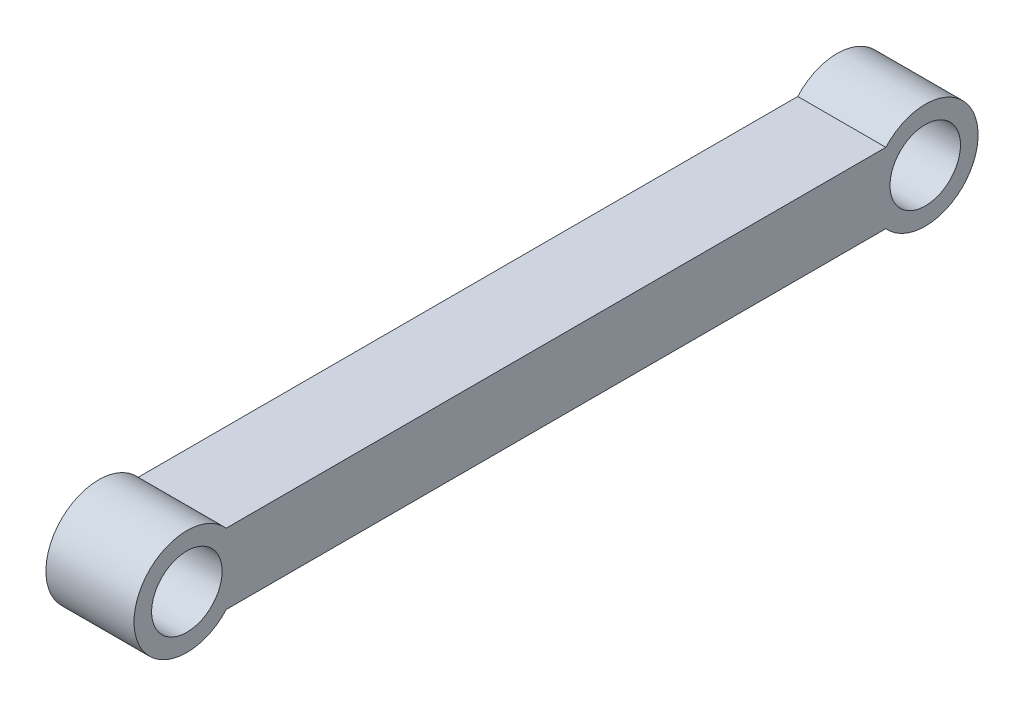
SolidWorks part; units mm, degrees
material "Thornel Mat VMA"
ref_plane "Front Plane" through (0, 0, 0) normal (0, 0, 1) x (1, 0, 0)
ref_plane "Top Plane" through (0, 0, 0) normal (0, 1, 0) x (1, 0, 0)
ref_plane "Right Plane" through (0, 0, 0) normal (1, 0, 0) x (0, 0, -1)
sketch "LinkFrame" plane through (0, 0, 0) normal (1, 0, 0) x (0, 0, -1)
  line L0 (-578.5355, -226.2633) -> (259.6545, -226.2633) construction
  line L1 (-533.8142, -186.2633) -> (214.9331, -186.2633)
  line L2 (-533.8142, -266.2633) -> (214.9331, -266.2633)
  arc A1 (214.9331, -266.2633) -> (214.9331, -186.2633) centre (259.6545, -226.2633) ccw
  arc A2 (-533.8142, -186.2633) -> (-533.8142, -266.2633) centre (-578.5355, -226.2633) ccw
  circle A5 centre (-578.5355, -226.2633) radius 40
  circle A6 centre (259.6545, -226.2633) radius 40
  dimension "D1" = 120
  dimension "D2" = 120
  dimension "D5" = 80
  dimension "D6" = 80
  dimension "D3" = 838.19
  dimension "D4" = 80
  dimension "D7" = 44.7214
  dimension "D8" = 44.7214
extrude "Boss-Extrude1" add sketch "LinkFrame" along normal blind 100
equation "\"D1@LinkFrame\" = 1.5 * \"HoleMountDiameter@PrintingPress.Assembly\""
equation "\"D2@LinkFrame\" = 1.5 * \"HoleMountDiameter@PrintingPress.Assembly\""
equation "\"LinkLength\" = 60cm + 23.819cm"
equation "\"D3@LinkFrame\" = \"LinkLength\""
equation "\"D4@LinkFrame\" = \"HoleMountDiameter@PrintingPress.Assembly\""
equation "\"D5@LinkFrame\"=\"HoleMountDiameter@PrintingPress.Assembly\""
equation "\"D6@LinkFrame\"=\"HoleMountDiameter@PrintingPress.Assembly\""
equation "\"D1@Boss-Extrude1\"=\"RivetLength@PrintingPress.Assembly\""
